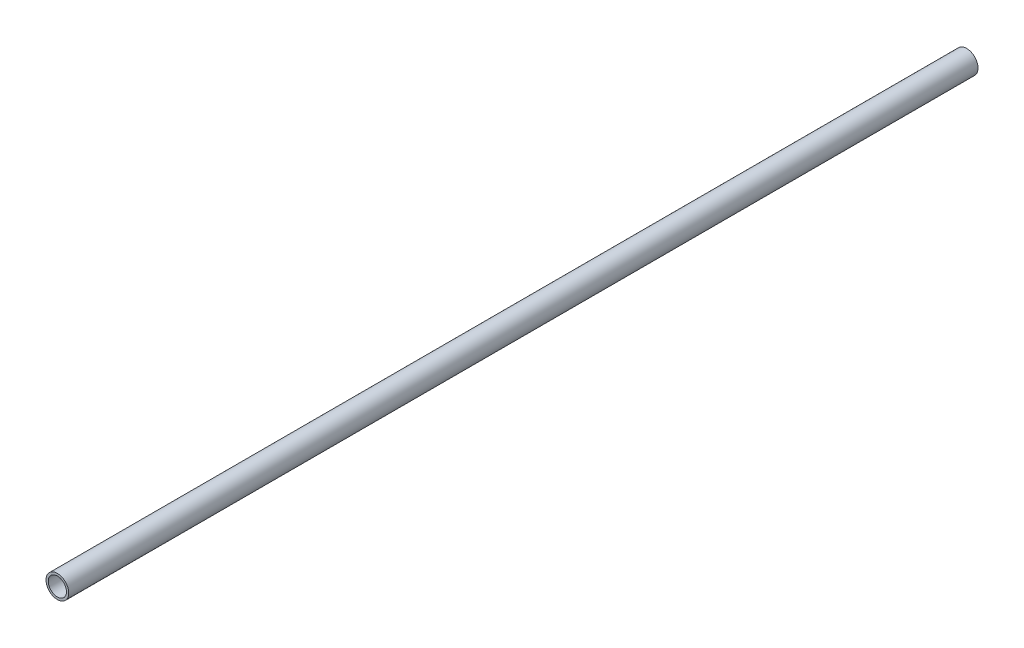
SolidWorks part; units mm, degrees
material "Thornel Mat VMA"
ref_plane "Front Plane" through (0, 0, 0) normal (0, 0, 1) x (1, 0, 0)
ref_plane "Top Plane" through (0, 0, 0) normal (0, 1, 0) x (1, 0, 0)
ref_plane "Right Plane" through (0, 0, 0) normal (1, 0, 0) x (0, 0, -1)
sketch "Sketch1" plane through (0, 0, 0) normal (0, 0, 1) x (1, 0, 0)
  circle A0 centre (0, 0) radius 4
  circle A1 centre (0, 0) radius 5
  dimension "D1" = 10
  dimension "D2" = 8
extrude "Boss-Extrude1" add sketch "Sketch1" along normal mid plane 400.05
